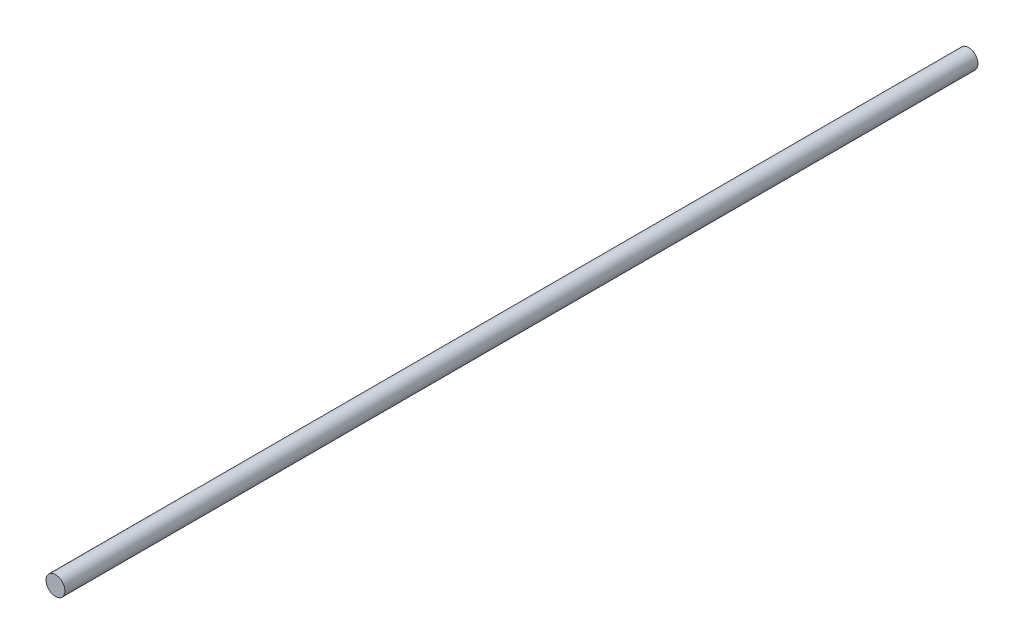
SolidWorks part; units mm, degrees
material "AISI 316 Stainless Steel Sheet (SS)"
ref_plane "Front (1)" through (0, 0, 0) normal (0, 0, 1) x (1, 0, 0)
ref_plane "Top (2)" through (0, 0, 0) normal (0, 1, 0) x (1, 0, 0)
ref_plane "Right (3)" through (0, 0, 0) normal (1, 0, 0) x (0, 0, -1)
ref_axis "X Axis" through (13.5064, 0, 0) along (-1, 0, 0)
ref_axis "Y Axis" through (0, 12.3593, 0) along (0, -1, 0)
ref_axis "Z Axis" through (0, 0, 14.1119) along (0, 0, -1)
sketch "Sketch2" plane through (0, 0, 0) normal (1, 0, 0) x (0, 0, -1)
  line L1 (0, 0) -> (385, 0)
  line L2 (0, 0) -> (0, 4)
  line L3 (0, 4) -> (385, 4)
  line L4 (385, 0) -> (385, 4)
  dimension "D1" = 385
  dimension "D2" = 4
revolve "Revolve1" add sketch "Sketch2" angle 360 about L1
